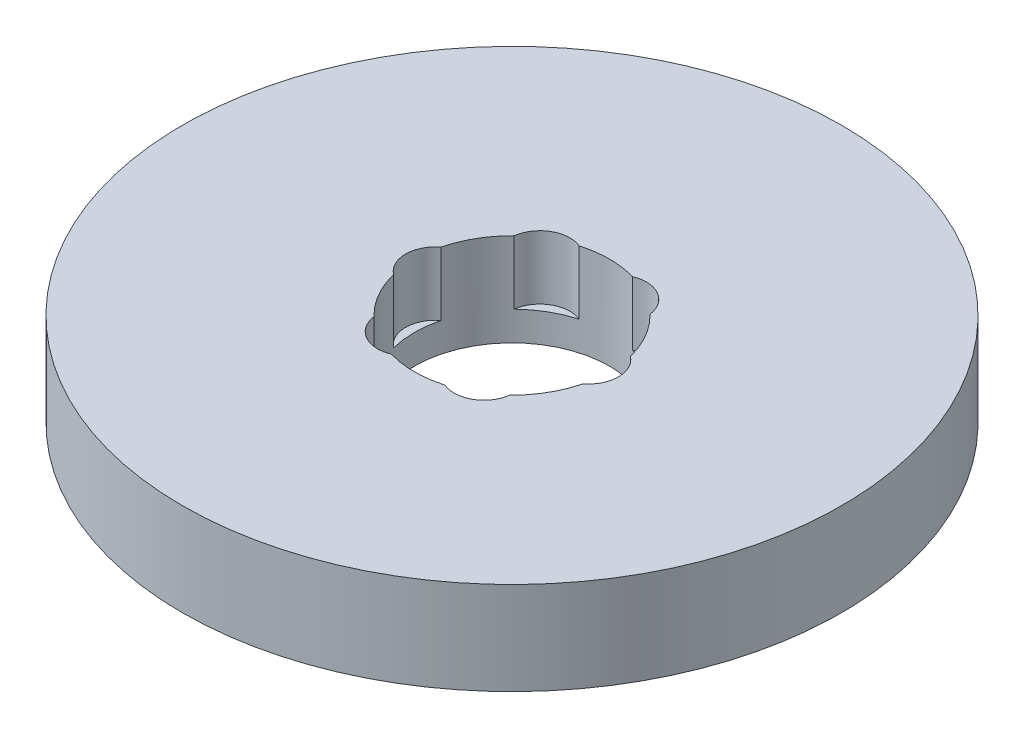
SolidWorks part; units mm, degrees
ref_plane "Front Plane" through (0, 0, 0) normal (0, 0, 1) x (1, 0, 0)
ref_plane "Top Plane" through (0, 0, 0) normal (0, 1, 0) x (1, 0, 0)
ref_plane "Right Plane" through (0, 0, 0) normal (1, 0, 0) x (0, 0, -1)
sketch "Sketch1" plane through (0, 0, 0) normal (0, 1, 0) x (1, 0, 0)
  circle A0 centre (0, 0) radius 67.5
  dimension "FLANGE_OD" = 135
extrude "Boss-Extrude1" add sketch "Sketch1" along normal blind 19
sketch "Sketch2" plane through (0, 0, 0) normal (0, 1, 0) x (1, 0, 0)
  circle A0 centre (0, 0) radius 20
  dimension "BORE_D" = 40
extrude "Cut-Extrude1" cut sketch "Sketch2" along normal through all
sketch "Sketch3" plane through (0, 19, 0) normal (0, 1, 0) x (1, 0, 0)
  circle A0 centre (0, 0) radius 15.6721 construction
  circle A1 centre (-15.6721, 0) radius 6.1268
  dimension "BOLT_D" = 12.2536
  dimension "BOLT_PCD" = 31.3443
extrude "Cut-Extrude2" cut sketch "Sketch3" against normal blind 13.0194
pattern_circular "CirPattern1" count 6 over 360 about axis through (0, 0, 0) along (0, 1, 0) of "Cut-Extrude2"
